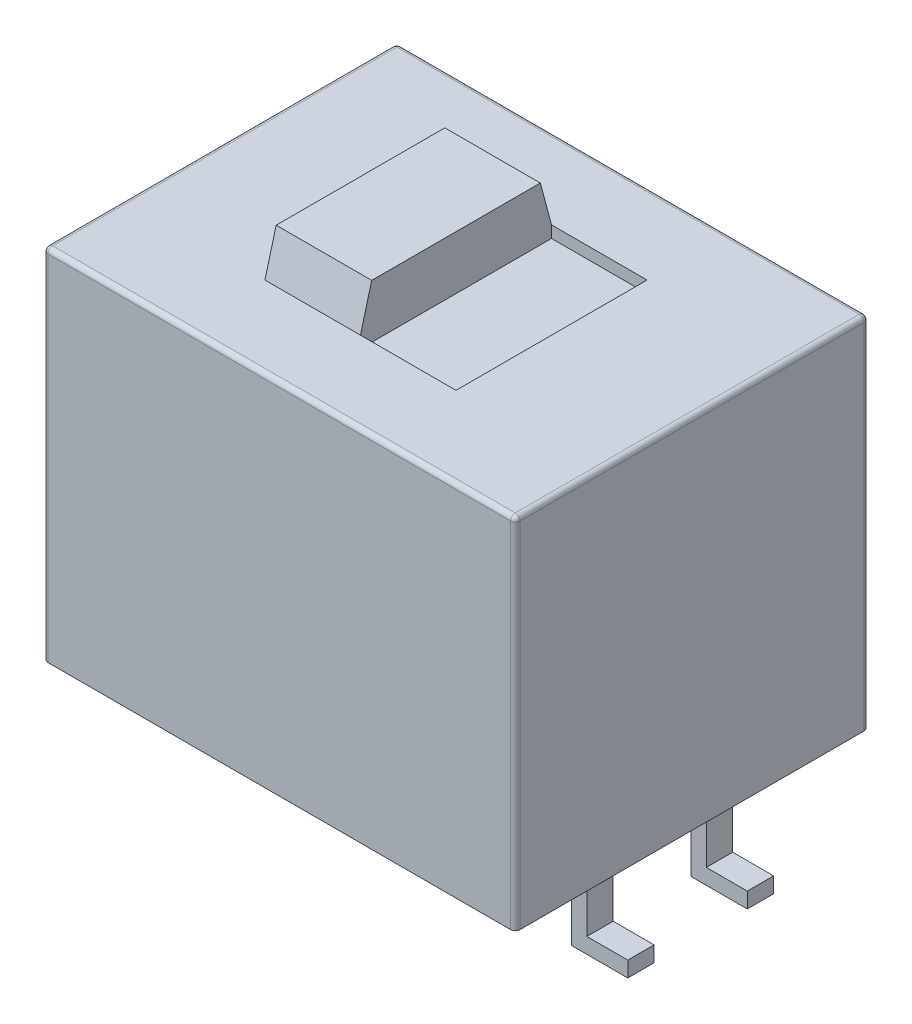
SolidWorks part; units mm, degrees
ref_plane "Front Plane" through (0, 0, 0) normal (0, 0, 1) x (1, 0, 0)
ref_plane "Top Plane" through (0, 0, 0) normal (0, 1, 0) x (1, 0, 0)
ref_plane "Right Plane" through (0, 0, 0) normal (1, 0, 0) x (0, 0, -1)
sketch "Sketch1" plane through (0, 0, 0) normal (0, 1, 0) x (1, 0, 0)
  line L1 (5.015, 3.755) -> (-5.015, 3.755)
  line L2 (5.015, 3.755) -> (5.015, -3.755)
  line L3 (5.015, -3.755) -> (-5.015, -3.755)
  line L4 (-5.015, 3.755) -> (-5.015, -3.755)
  line L5 (5.015, 3.755) -> (-5.015, -3.755) construction
  line L6 (5.015, -3.755) -> (-5.015, 3.755) construction
  point P0 (0, 0)
  dimension "D1" = 10.03
  dimension "D2" = 7.51
extrude "Boss-Extrude1" add sketch "Sketch1" along normal blind 7.62
sketch "Sketch2" plane through (0, 7.62, 0) normal (0, 1, 0) x (1, 0, 0)
  line L1 (-2.03, 2.03) -> (0, 2.03)
  line L2 (-2.03, 2.03) -> (-2.03, -2.03) construction
  line L3 (-2.03, -2.03) -> (0, -2.03)
  line L4 (0, 2.03) -> (0, -2.03)
  line L5 (-2.03, 2.03) -> (0, -2.03) construction
  line L6 (-2.03, -2.03) -> (0, 2.03) construction
  line L11 (-2.03, 2.03) -> (2.03, 2.03) construction
  line L12 (-2.03, 2.03) -> (-2.03, -2.03)
  line L13 (-2.03, -2.03) -> (2.03, -2.03) construction
  line L14 (2.03, 2.03) -> (2.03, -2.03) construction
  point P0 (-1.015, 0)
  dimension "D1" = 4.06
  dimension "D2" = 2.03
  dimension "D3" = 4.06
extrude "Boss-Extrude2" add sketch "Sketch2" along normal blind 0.89
chamfer "Chamfer1" distance 0.89 angle 15 2 edges at (-1.015, 8.51, -2.03) (-1.015, 8.51, 2.03) first distance on face at (-1.015, 8.065, -2.03) first distance on face at (-1.015, 8.065, 2.03)
sketch "Sketch3" plane through (0, 7.62, 0) normal (0, 1, 0) x (1, 0, 0)
  line L0 (0, 2.03) -> (-2.03, 2.03) construction
  line L1 (0, -2.03) -> (2.03, -2.03)
  line L2 (0, -2.03) -> (0, 2.03)
  line L3 (0, 2.03) -> (2.03, 2.03)
  line L4 (2.03, -2.03) -> (2.03, 2.03)
  dimension "D1" = 2.03
extrude "Cut-Extrude1" cut sketch "Sketch3" against normal blind 0.25
ref_plane "Plane1" through (0, 0, 1.27) normal (0, 0, 1) x (1, 0, 0)
ref_plane "Plane2" through (0, 0, -1.27) normal (0, 0, 1) x (1, 0, 0)
sketch "Sketch4" plane through (0, 0, 1.27) normal (0, 0, 1) x (1, 0, 0)
  line L0 (-4, 0) -> (-4, -1.85)
  line L1 (-5.015, 0) -> (5.015, 0) construction
  line L2 (-4, -1.85) -> (-5.2, -1.85)
  line L3 (-5.2, -1.85) -> (-5.2, -1.52)
  line L4 (-5.2, -1.52) -> (-4.33, -1.52)
  line L5 (-4.33, -1.52) -> (-4.33, 0)
  line L6 (-4.33, 0) -> (-4, 0)
  line L7 (-5.015, 7.62) -> (5.015, 7.62) construction
  line L9 (0, 0) -> (0, 7.62) construction
  line L10 (4.33, 0) -> (4, 0)
  line L11 (4.33, -1.52) -> (4.33, 0)
  line L12 (5.2, -1.52) -> (4.33, -1.52)
  line L13 (5.2, -1.85) -> (5.2, -1.52)
  line L14 (4, -1.85) -> (5.2, -1.85)
  line L15 (4, 0) -> (4, -1.85)
  point P19 (0, 0)
  dimension "D1" = 0.33
  dimension "D2" = 9.47
  dimension "D3" = 0.33
  dimension "D4" = 8
  dimension "D5" = 10.4
extrude "Boss-Extrude3" add sketch "Sketch4" along normal mid plane 0.56 contours L10 L15 L14 L13 L12 L11 | L2 L3 L4 L5 L6 L0 region at (4.3079, -0.76, 1.27)
pattern_linear "LPattern1" count 2 spacing 2.54 along (0, 0, -1) of "Boss-Extrude3"
fillet "Fillet1" radius 0.1 8 edges at (5.015, 3.81, 3.755) (5.015, 3.81, -3.755) (-5.015, 3.81, -3.755) (-5.015, 3.81, 3.755) (5.015, 7.62, 0) (0, 7.62, 3.755) (0, 7.62, -3.755) (-5.015, 7.62, 0)
